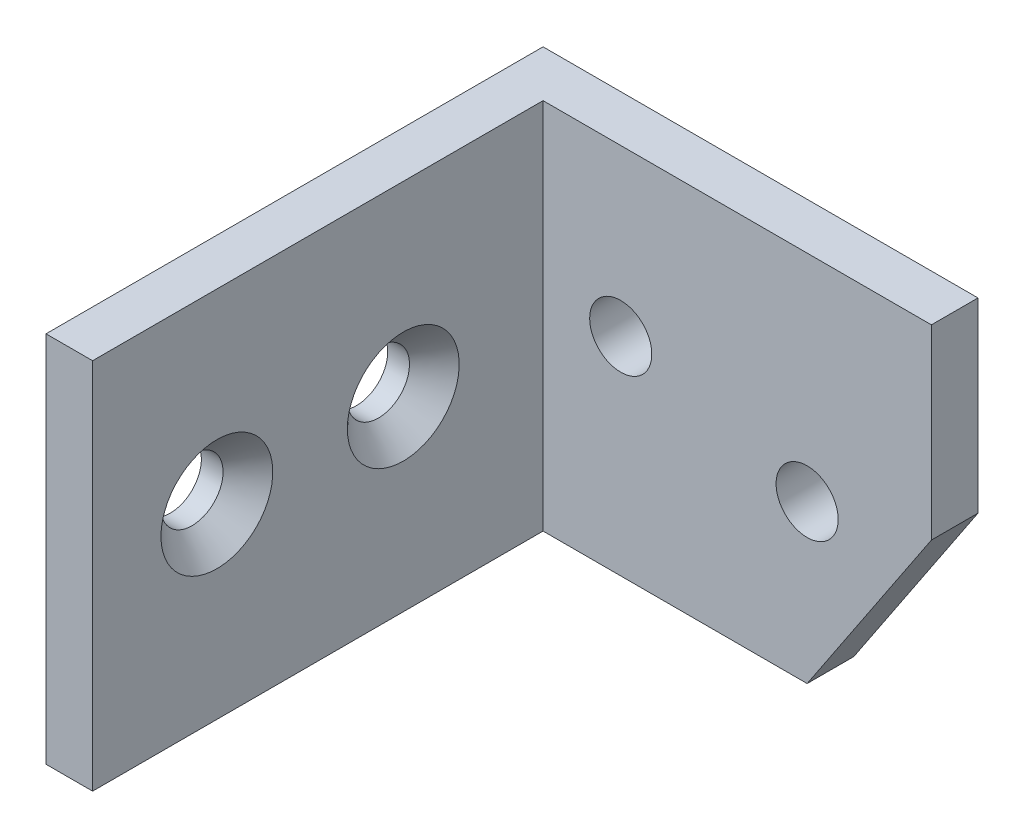
SolidWorks part; units mm, degrees
material "6061 Alloy"
ref_plane "Front Plane" through (0, 0, 0) normal (0, 0, 1) x (1, 0, 0)
ref_plane "Top Plane" through (0, 0, 0) normal (0, 1, 0) x (1, 0, 0)
ref_plane "Right Plane" through (0, 0, 0) normal (1, 0, 0) x (0, 0, -1)
sketch "Sketch1" plane through (0, 0, 0) normal (0, 1, 0) x (1, 0, 0)
  line L0 (0, 0) -> (0, 50.8)
  line L1 (0, 50.8) -> (44.45, 50.8)
  line L2 (4.7625, 0) -> (4.7625, 46.0375)
  line L3 (4.7625, 46.0375) -> (44.45, 46.0375)
  line L4 (0, 0) -> (4.7625, 0)
  line L5 (44.45, 50.8) -> (44.45, 46.0375)
  dimension "D2" = 44.45
  dimension "D3" = 50.8
  dimension "D1" = 4.7625
extrude "Boss-Extrude1" add sketch "Sketch1" along normal blind 38.1
sketch "Sketch2" plane through (0, 0, -50.8) normal (0, 0, -1) x (-1, 0, 0)
  line L0 (0, 24.6103) -> (-44.45, 12.7) construction
  line L1 (0, 38.1) -> (0, 0) construction
  line L2 (-44.45, 38.1) -> (-44.45, 0) construction
  line L3 (-44.45, 0) -> (0, 0) construction
  line L4 (-44.45, 38.1) -> (0, 38.1) construction
  circle A0 centre (-12.7, 21.2074) radius 3.175
  circle A1 centre (-31.75, 16.103) radius 3.175
  dimension "D3" = 6.35
  dimension "D4" = 6.35
  dimension "D5" = 12.7
  dimension "D6" = 19.05
  dimension "D1" = 12.7
  dimension "D2" = 15
extrude "Cut-Extrude1" cut sketch "Sketch2" against normal up to next
sketch "Sketch4" plane through (0, 0, 0) normal (-1, 0, 0) x (0, 0, 1)
  line L0 (0, 38.1) -> (0, 0) construction
  line L1 (-50.8, 38.1) -> (0, 38.1) construction
  circle A0 centre (-12.7, 19.05) radius 3.175
  circle A1 centre (-31.75, 19.05) radius 3.175
  dimension "D1" = 6.35
  dimension "D2" = 6.35
  dimension "D3" = 12.7
  dimension "D4" = 19.05
  dimension "D5" = 19.05
  dimension "D6" = 19.05
extrude "Cut-Extrude2" cut sketch "Sketch4" against normal up to next
sketch "Sketch5" plane through (0, 0, -50.8) normal (0, 0, -1) x (-1, 0, 0)
  line L0 (-31.75, 0) -> (-44.45, 19.05)
  line L1 (-44.45, 0) -> (0, 0) construction
  line L2 (-44.45, 38.1) -> (-44.45, 0) construction
  dimension "D1" = 12.7
  dimension "D2" = 19.05
extrude "Cut-Extrude3" cut sketch "Sketch5" against normal through all and the other way through all
chamfer "Chamfer1" distance 2.54 angle 45 2 edges at (4.7625, 19.05, -9.525) (4.7625, 19.05, -28.575)
